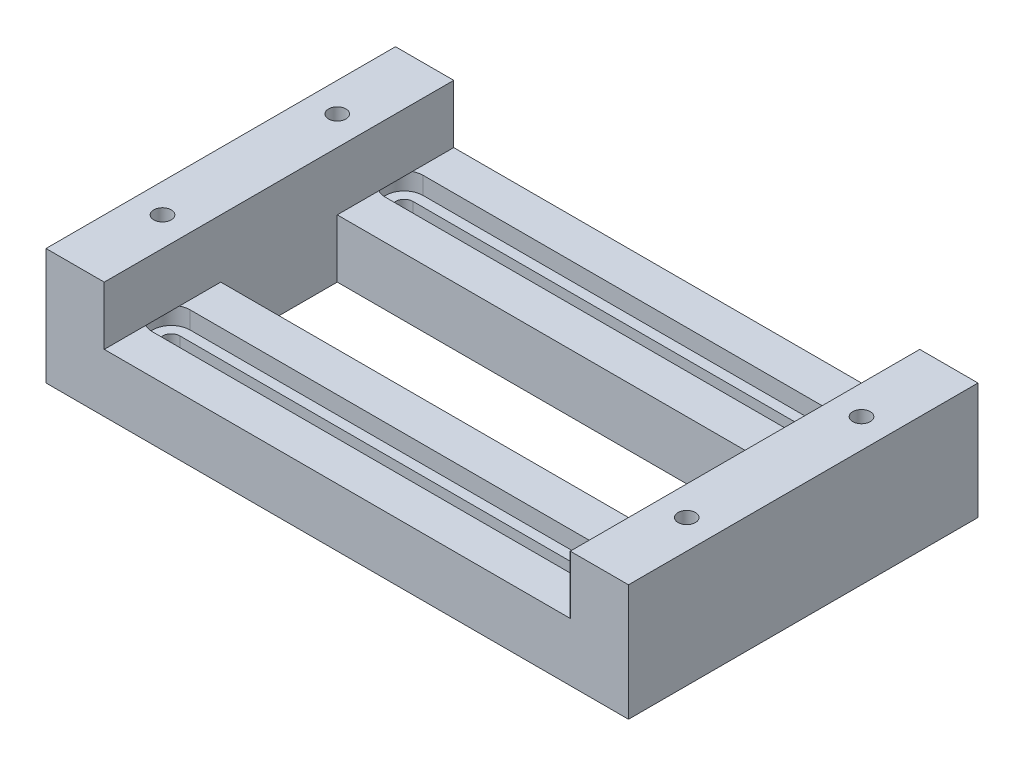
SolidWorks part; units mm, degrees
ref_plane "Front Plane" through (0, 0, 0) normal (0, 0, 1) x (1, 0, 0)
ref_plane "Top Plane" through (0, 0, 0) normal (0, 1, 0) x (1, 0, 0)
ref_plane "Right Plane" through (0, 0, 0) normal (1, 0, 0) x (0, 0, -1)
sketch "Sketch1" plane through (0, 0, 0) normal (0, 1, 0) x (1, 0, 0)
  line L0 (10, 40) -> (10, 20)
  line L1 (0, 0) -> (100, 0)
  line L2 (0, 0) -> (0, 60)
  line L3 (0, 60) -> (100, 60)
  line L4 (100, 0) -> (100, 60)
  line L5 (10, 20) -> (90, 20)
  line L6 (90, 20) -> (90, 40)
  line L7 (90, 40) -> (10, 40)
  line L8 (11.5, 10) -> (88.5, 10) construction
  line L9 (11.5, 11.5) -> (88.5, 11.5)
  line L10 (11.5, 8.5) -> (88.5, 8.5)
  line L11 (88.5, 50) -> (11.5, 50) construction
  line L12 (88.5, 48.5) -> (11.5, 48.5)
  line L13 (50, 0) -> (50, 20) construction
  line L14 (50, 40) -> (50, 60)
  line L15 (88.5, 51.5) -> (11.5, 51.5)
  circle A7 centre (5, 45) radius 1.5
  arc A22 (11.5, 11.5) -> (11.5, 8.5) centre (11.5, 10) ccw
  arc A23 (88.5, 8.5) -> (88.5, 11.5) centre (88.5, 10) ccw
  arc A24 (88.5, 48.5) -> (88.5, 51.5) centre (88.5, 50) ccw
  arc A25 (11.5, 51.5) -> (11.5, 48.5) centre (11.5, 50) ccw
  circle A29 centre (5, 15) radius 1.5
  circle A46 centre (95, 45) radius 1.5
  circle A47 centre (95, 15) radius 1.5
  point P13 (0, 0)
  point P14 (50, 50)
  point P17 (50, 10)
  point P22 (50, 50)
  point P33 (50, 10)
  point P34 (90, 10)
  point P35 (10, 10)
  point P36 (90, 50)
  point P37 (10, 50)
  dimension "D25" = 3
  dimension "D4" = 3
  dimension "D18" = 3
  dimension "D19" = 3
  dimension "D1" = 60
  dimension "D2" = 100
  dimension "D3" = 10
  dimension "D22" = 20
  dimension "D23" = 20
  dimension "D24" = 10
  dimension "D28" = 15
  dimension "D5" = 15
  dimension "D6" = 5
  dimension "D8" = 5
  dimension "D9" = 15
  dimension "D13" = 5
  dimension "D16" = 5
  dimension "D17" = 15
  dimension "D7" = 3
  dimension "D10" = 3
  dimension "D11" = 80
  dimension "D12" = 80
extrude "Boss-Extrude1" add sketch "Sketch1" along normal blind 10 contours L1 L4 L3 L2 A47 A46 A29 A7 L7 L6 L5 L0 region at (75, 0, -58.8338)
sketch "Sketch3" plane through (0, 10, 0) normal (0, 1, 0) x (1, 0, 0)
  line L4 (88.5, 53.25) -> (11.5, 53.25)
  line L5 (11.5, 46.75) -> (88.5, 46.75)
  line L6 (88.5, 13.25) -> (11.5, 13.25)
  line L7 (11.5, 6.75) -> (88.5, 6.75)
  line L8 (88.5, 13.25) -> (11.5, 13.25)
  line L9 (11.5, 6.75) -> (88.5, 6.75)
  line L10 (88.5, 53.25) -> (11.5, 53.25)
  line L11 (11.5, 46.75) -> (88.5, 46.75)
  arc A4 (88.5, 46.75) -> (88.5, 53.25) centre (88.5, 50) ccw
  arc A5 (11.5, 53.25) -> (11.5, 46.75) centre (11.5, 50) ccw
  arc A6 (11.5, 13.25) -> (11.5, 6.75) centre (11.5, 10) ccw
  arc A7 (88.5, 6.75) -> (88.5, 13.25) centre (88.5, 10) ccw
  arc A8 (11.5, 13.25) -> (11.5, 6.75) centre (11.5, 10) ccw
  arc A9 (88.5, 6.75) -> (88.5, 13.25) centre (88.5, 10) ccw
  arc A10 (88.5, 46.75) -> (88.5, 53.25) centre (88.5, 50) ccw
  arc A11 (11.5, 53.25) -> (11.5, 46.75) centre (11.5, 50) ccw
  dimension "D1" = 1.75
  dimension "D2" = 1.75
extrude "Cut-Slot insets" cut sketch "Sketch3" against normal blind 3
sketch "Sketch5" plane through (0, 10, 0) normal (0, 1, 0) x (1, 0, 0)
  line L2 (0, 60) -> (100, 60) construction
  line L3 (10, 60) -> (0, 60)
  line L4 (0, 60) -> (0, 0)
  line L5 (0, 0) -> (10, 0)
  line L6 (0, 0) -> (100, 0) construction
  line L9 (90, 0) -> (100, 0)
  line L10 (100, 0) -> (100, 60)
  line L11 (100, 60) -> (90, 60)
  line L20 (90, 60) -> (90, 0)
  line L21 (90, 20) -> (90, 40) construction
  line L22 (10, 0) -> (10, 60)
  line L23 (10, 40) -> (10, 20) construction
  circle A0 centre (95, 45) radius 1.5
  circle A3 centre (95, 15) radius 1.5
  circle A5 centre (5, 15) radius 1.5
  circle A8 centre (5, 45) radius 1.5
  circle A9 centre (5, 15) radius 1.5 construction
  circle A10 centre (5, 45) radius 1.5 construction
  circle A11 centre (95, 45) radius 1.5 construction
  circle A12 centre (95, 15) radius 1.5 construction
extrude "Boss-Extrude3" add sketch "Sketch5" along normal blind 10
sketch "Sketch6" plane through (0, 0, 0) normal (0, -1, 0) x (1, 0, 0)
  circle A0 centre (5, -45) radius 3.75
  circle A2 centre (5, -15) radius 3.75
  circle A3 centre (95, -15) radius 3.75
  circle A5 centre (95, -45) radius 3.75
  dimension "D1" = 7.5
  dimension "D3" = 7.5
  dimension "D4" = 7.5
  dimension "D6" = 7.5
extrude "Cut-Extrude1" cut sketch "Sketch6" against normal blind 2.5
equation "\"boltdiameter\"=3"
equation "\"D25@Sketch1\"=\"boltdiameter\""
equation "\"D4@Sketch1\"=\"boltdiameter\""
equation "\"D18@Sketch1\"=\"boltdiameter\""
equation "\"D19@Sketch1\"=\"boltdiameter\""
equation "\"boltfacediameter\"=7"
equation "\"boltFaceOffset\"= 1.75"
equation "\"D1@Sketch3\" = \"boltFaceOffset\""
equation "\"D2@Sketch3\" = \"boltFaceOffset\""
equation "\"screwInset\"=7.5"
equation "\"D1@Sketch6\"=\"screwInset\""
equation "\"D3@Sketch6\"=\"screwInset\""
equation "\"D4@Sketch6\"=\"screwInset\""
equation "\"D6@Sketch6\"=\"screwInset\""
equation "\"D7@Sketch1\"=\"boltdiameter\""
equation "\"D10@Sketch1\"=\"boltdiameter\""
equation "\"slotLength\"=80"
equation "\"D11@Sketch1\"=\"slotLength\""
equation "\"D12@Sketch1\"=\"slotLength\""
